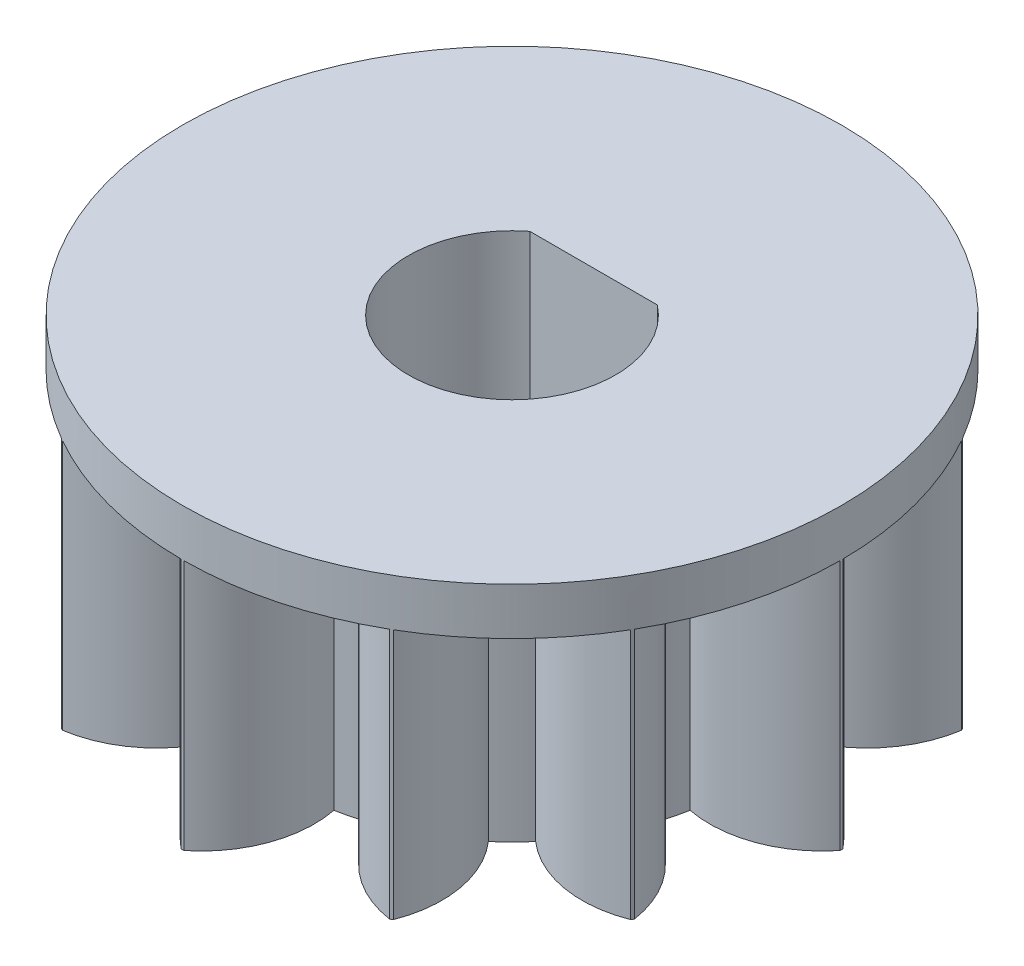
SolidWorks part; units mm, degrees
material "3D printed plastic"
ref_plane "Front Plane" through (0, 0, 0) normal (0, 0, 1) x (1, 0, 0)
ref_plane "Top Plane" through (0, 0, 0) normal (0, 1, 0) x (1, 0, 0)
ref_plane "Right Plane" through (0, 0, 0) normal (1, 0, 0) x (0, 0, -1)
ref_axis "Axis1" through (0, 20.85, 0) along (0, -1, 0)
sketch "Sketch6" plane through (0, 0, 0) normal (0, 1, 0) x (-1, 0, 0)
  line L0 (0, 9) -> (0, 8.625) construction
  line L1 (0, 8.625) -> (0, 8.25) construction
  line L2 (0, 8.25) -> (0, 7.875) construction
  line L3 (0, 7.875) -> (0, 7.5) construction
  line L4 (0, 7.5) -> (0, 7.125) construction
  line L5 (0, 9) -> (0, 9.375) construction
  line L6 (0, 9.375) -> (0, 9.75) construction
  line L7 (0, 9.75) -> (0, 10.125) construction
  line L8 (0, 10.125) -> (0, 10.5) construction
  line L9 (-2.7176, 10.1422) -> (-0.2588, 0.9659) construction
  line L10 (0.2588, 0.9659) -> (2.7176, 10.1422) construction
  line L11 (-2.3294, 8.6933) -> (-1.1747, 8.923) construction
  line L12 (-1.1747, 8.923) -> (0, 9) construction
  line L13 (0, 9) -> (1.1747, 8.923) construction
  line L14 (1.1747, 8.923) -> (2.3294, 8.6933) construction
  line L15 (-2.2082, 7.6917) -> (2.2082, 7.6917) construction
  line L16 (-1.1747, 8.923) -> (2.2082, 7.6917) construction
  line L17 (-1.8441, 6.8822) -> (-0.2588, 0.9659)
  line L18 (0.2588, 0.9659) -> (1.8441, 6.8822)
  line L19 (-0.2588, 0.9659) -> (0, 0) construction
  line L20 (0, 0) -> (0.2588, 0.9659) construction
  arc A0 (2.7176, 10.1422) -> (-2.7176, 10.1422) centre (0, 0) ccw construction
  arc A1 (1.8441, 6.8822) -> (1.3249, 7.0007) centre (0, 0) ccw
  arc A2 (2.3294, 8.6933) -> (1.1747, 8.923) centre (0, 0) ccw construction
  arc A3 (-0.0444, 10.4999) -> (-1.3249, 7.0007) centre (2.2082, 7.6917) ccw
  arc A4 (0.0444, 10.4999) -> (1.3249, 7.0007) centre (-2.2082, 7.6917) cw
  arc A5 (0, 9) -> (-1.1747, 8.923) centre (0, 0) ccw construction
  arc A6 (-1.1747, 8.923) -> (-2.3294, 8.6933) centre (0, 0) ccw construction
  arc A7 (0, 9) -> (1.1747, 8.923) centre (0, 0) cw construction
  arc A8 (-1.3249, 7.0007) -> (-1.8441, 6.8822) centre (0, 0) ccw
  arc A9 (-1.3249, 7.0007) -> (1.3249, 7.0007) centre (0, 0) cw construction
  arc A10 (-0.0444, 10.4999) -> (0.0444, 10.4999) centre (0, 0) cw
  arc A13 (0.2588, 0.9659) -> (-0.2588, 0.9659) centre (0, 0) ccw
  dimension "D1" = 18
  dimension "D4" = 3.6
  dimension "D6" = 1
  dimension "D2" = 1.5
  dimension "D3" = 30
  dimension "D5" = 70
extrude "Boss-Extrude2" add sketch "Sketch6" along normal blind 8
pattern_circular "CirPattern4" count 12 over 360 about axis through (0, 20.85, 0) along (0, -1, 0) of "Boss-Extrude2"
sketch "Sketch7" plane through (0, 8, 0) normal (0, 1, 0) x (1, 0, 0)
  line L0 (2.0322, 2.6) -> (-2.0322, 2.6)
  arc A0 (-2.0322, 2.6) -> (2.0322, 2.6) centre (0, 0) ccw
  dimension "D1" = 3.3
  dimension "D2" = 2.6
extrude "Cut-Extrude1" cut sketch "Sketch7" against normal through all
sketch "Sketch8" plane through (0, 8, 0) normal (0, 1, 0) x (1, 0, 0)
  line L0 (2.0322, 2.6) -> (-2.0322, 2.6)
  line L1 (2.0322, 2.6) -> (-2.0322, 2.6) construction
  circle A0 centre (0, 0) radius 10.5
  arc A1 (-2.0322, 2.6) -> (2.0322, 2.6) centre (0, 0) ccw
  arc A2 (-2.0322, 2.6) -> (2.0322, 2.6) centre (0, 0) ccw construction
extrude "Boss-Extrude3" add sketch "Sketch8" along normal blind 1.5
